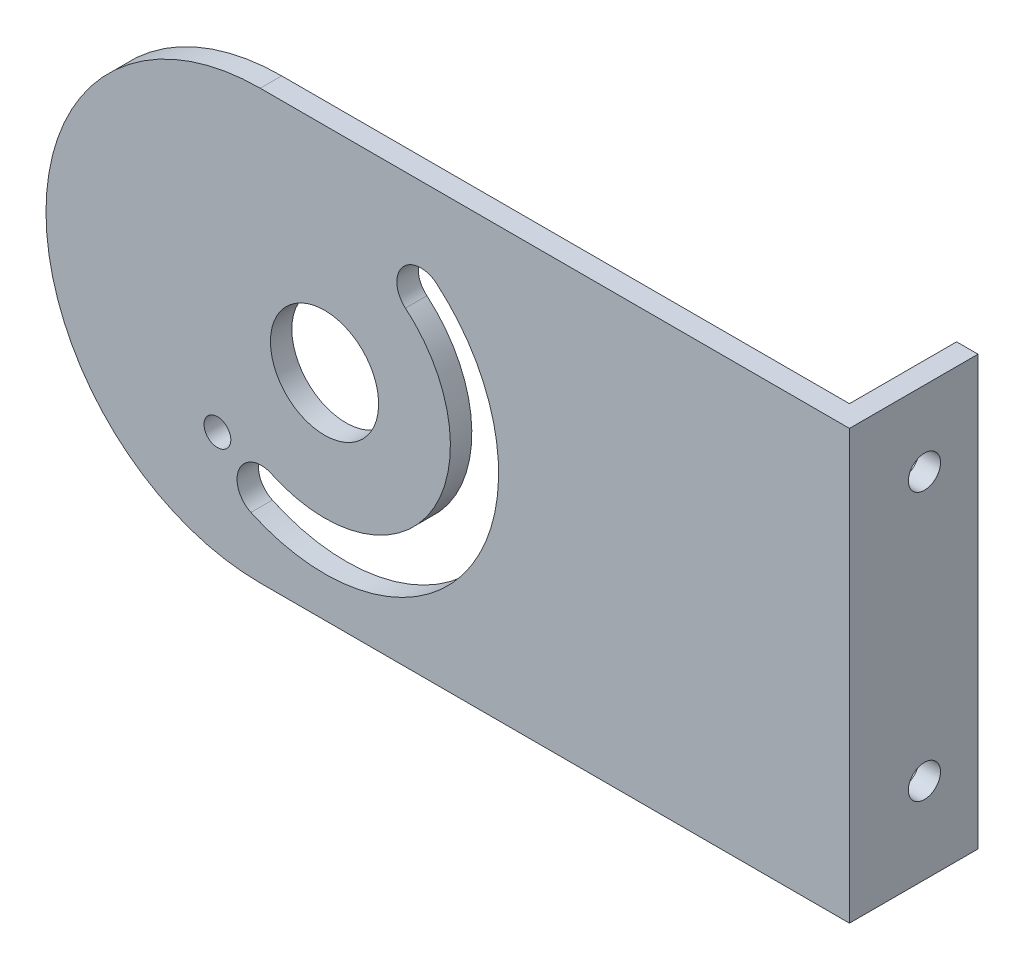
SolidWorks part; units mm, degrees
ref_plane "前视基准面" through (0, 0, 0) normal (0, 0, 1) x (1, 0, 0)
ref_plane "上视基准面" through (0, 0, 0) normal (0, 1, 0) x (1, 0, 0)
ref_plane "右视基准面" through (0, 0, 0) normal (1, 0, 0) x (0, 0, -1)
other "Configuration Table"
sketch "草图2" plane through (0, 0, 0) normal (0, 0, 1) x (1, 0, 0)
  line L0 (0, 0) -> (0, 40)
  line L1 (0, 40) -> (75, 40)
  line L2 (75, 40) -> (75, 0)
  line L3 (75, 0) -> (0, 0)
  dimension "D1" = 40
  dimension "D2" = 75
extrude "凸台-拉伸1" add sketch "草图2" along normal blind 2
sketch "草图3" plane through (0, 0, 0) normal (0, 0, -1) x (-1, 0, 0)
  line L0 (0, 40) -> (0, 0) construction
  line L6 (-75, 40) -> (0, 40) construction
  line L7 (-26, 20) -> (-35, 30.7238) construction
  line L8 (-26, 20) -> (-20.0822, 7.3122) construction
  circle A0 centre (-26, 20) radius 5.05
  circle A1 centre (-26, 20) radius 14 construction
  arc A3 (-35, 30.7238) -> (-20.0822, 7.3122) centre (-26, 20) ccw construction
  arc A4 (-36.4464, 32.4473) -> (-19.1311, 5.2731) centre (-26, 20) ccw
  arc A5 (-33.5536, 29.0003) -> (-21.0333, 9.3513) centre (-26, 20) ccw
  arc A6 (-33.5536, 29.0003) -> (-36.4464, 32.4473) centre (-35, 30.7238) ccw
  arc A7 (-19.1311, 5.2731) -> (-21.0333, 9.3513) centre (-20.0822, 7.3122) ccw
  circle A8 centre (-16, 10.202) radius 1.25
  point P13 (-37.8068, 12.4767)
  dimension "D1" = 10.1
  dimension "D4" = 28
  dimension "D5" = 20
  dimension "D8" = 4.5
  dimension "D9" = 2.5
  dimension "D2" = 26
  dimension "D6" = 165
  dimension "D7" = 9
  dimension "D10" = 10
extrude "切除-拉伸1" cut sketch "草图3" against normal through all
fillet "圆角1" radius 20 2 edges at (0, 40, 1) (0, 0, 1)
sketch "草图7" plane through (0, 0, 0) normal (0, 0, -1) x (-1, 0, 0)
  line L0 (-75, 40) -> (-20, 40) construction
  line L1 (-75, 0) -> (-73, 0)
  line L2 (-75, 0) -> (-75, 40)
  line L3 (-75, 40) -> (-73, 40)
  line L4 (-73, 0) -> (-73, 40)
  dimension "D1" = 2
extrude "凸台-拉伸3" add sketch "草图7" along normal blind 10
sketch "草图10" plane through (73, 0, 0) normal (-1, 0, 0) x (0, 0, 1)
  line L1 (0, 0) -> (0, 40) construction
  line L2 (-10, 40) -> (0, 40) construction
  circle A0 centre (-5, 33) radius 1.5
  circle A1 centre (-5, 8) radius 1.5
  dimension "D1" = 3
  dimension "D2" = 5
  dimension "D3" = 7
  dimension "D4" = 25
extrude "切除-拉伸4" cut sketch "草图10" against normal through all
